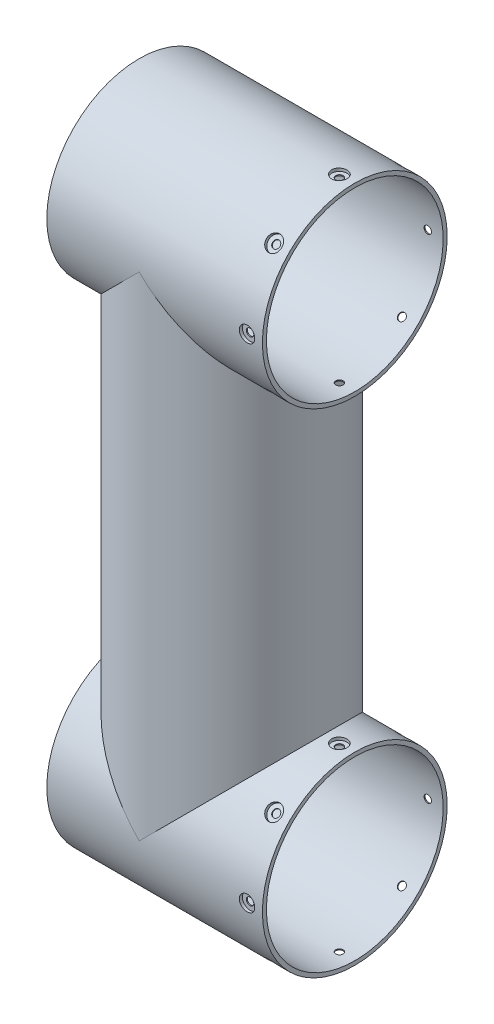
SolidWorks part; units mm, degrees
ref_plane "정면" through (0, 0, 0) normal (0, 0, 1) x (1, 0, 0)
ref_plane "윗면" through (0, 0, 0) normal (0, 1, 0) x (1, 0, 0)
ref_plane "우측면" through (0, 0, 0) normal (1, 0, 0) x (0, 0, -1)
sketch "스케치1" plane through (0, 0, 0) normal (0, 1, 0) x (1, 0, 0)
  circle A0 centre (0, 0) radius 30
  dimension "D1" = 60
extrude "보스-돌출1" add sketch "스케치1" along normal blind 160
sketch "스케치2" plane through (0, 0, 0) normal (1, 0, 0) x (0, 0, -1)
  line L0 (-30, 0) -> (30, 0) construction
  circle A0 centre (0, 0) radius 30
  dimension "D1" = 60
  dimension "D2" = 0
extrude "보스-돌출2" add sketch "스케치2" along normal blind 40 and the other way blind 30
sketch "스케치3" plane through (-30, 0, 0) normal (-1, 0, 0) x (0, 0, 1)
  circle A0 centre (0, 0) radius 28.7
  circle A1 centre (0, 0) radius 30 construction
  dimension "D1" = 1.3
extrude "컷-돌출1" cut sketch "스케치3" against normal through all
sketch "스케치4" plane through (0, 160, 0) normal (0, 1, 0) x (1, 0, 0)
  circle A0 centre (0, 0) radius 28.7
  arc A1 (0, 30) -> (-30, 0) centre (0, 0) ccw construction
  dimension "D1" = 1.3
extrude "컷-돌출2" cut sketch "스케치4" against normal blind 160
ref_plane "평면1" through (0, 80, 0) normal (0, 1, 0) x (1, 0, 0)
ref_plane "평면2" through (0, 0, -30) normal (0, 0, -1) x (-1, 0, 0)
sketch "스케치5" plane through (0, 0, -30) normal (0, 0, -1) x (-1, 0, 0)
  line L0 (-40, 30) -> (-40, -30) construction
  point P0 (-35, 0)
  dimension "D1" = 5
hole_wizard "M2 남비 머리 나사용 카운터보어1" positions "스케치6" profile "스케치7" counterbore size "M2" standard "ISO"
sketch "스케치6" plane through (0, 0, -30) normal (0, 0, -1) x (-1, 0, 0)
  point P0 (-35, 0)
sketch "스케치7" plane through (35, 0, -30) normal (1, 0, 0) x (0, 1, 0)
  line L0 (0, 0) -> (0, 10.721)
  line L1 (0, 10.721) -> (1.2, 10)
  line L2 (1.2, 10) -> (1.2, 1)
  line L3 (1.2, 1) -> (2.5, 1)
  line L4 (2.5, 1) -> (2.5, 0)
  line L5 (2.5, 0) -> (0, 0)
  line L10 (0, 10.721) -> (-1.2, 10) construction
  line L11 (0, -6.35) -> (0, 107.95) construction
  dimension "구멍 지름" = 2.4
  dimension "구멍 깊이" = 10
  dimension "카운터보어 지름" = 5
  dimension "카운터보어 깊이" = 1
  dimension "드릴 각도" = 118
pattern_circular "원형 패턴1" count 8 over 360 about axis through (40, 0, 0) along (1, 0, 0) of "M2 남비 머리 나사용 카운터보어1"
mirror "대칭 복사2" about plane through (0, 80, 0) normal (0, 1, 0) of "보스-돌출2", "컷-돌출1", "M2 남비 머리 나사용 카운터보어1", "원형 패턴1"
